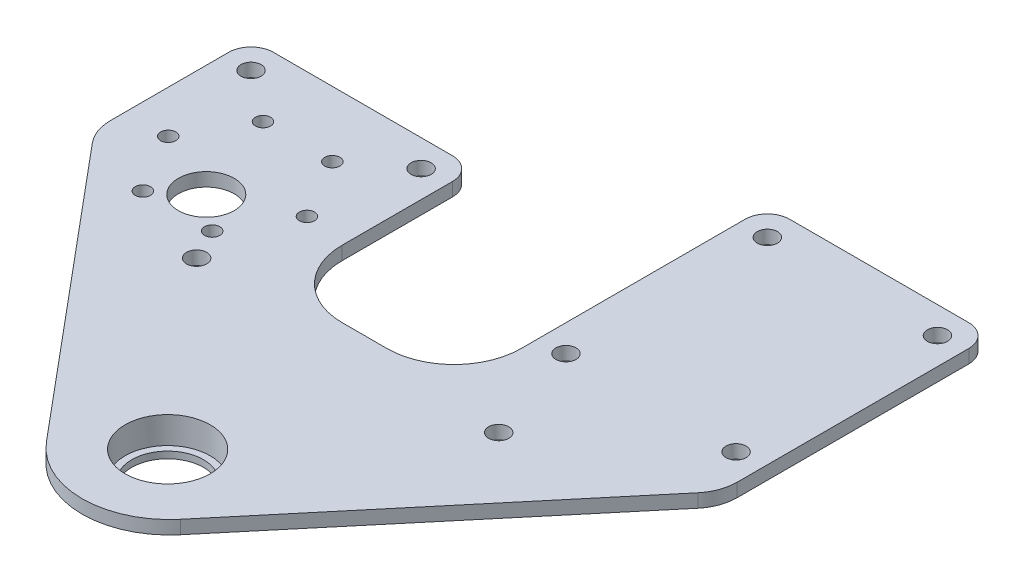
SolidWorks part; units mm, degrees
material "ABS"
ref_plane "Front Plane" through (0, 0, 0) normal (0, 0, 1) x (1, 0, 0)
ref_plane "Top Plane" through (0, 0, 0) normal (0, 1, 0) x (1, 0, 0)
ref_plane "Right Plane" through (0, 0, 0) normal (1, 0, 0) x (0, 0, -1)
sketch "Sketch2" plane through (0, 0, 0) normal (0, 1, 0) x (1, 0, 0)
  line L0 (-69.9951, 83.6231) -> (-69.9951, 57.2559)
  line L1 (-67.6634, 50.8374) -> (-14.9531, -12.1356)
  line L2 (14.9531, -12.1356) -> (67.6634, 50.8374)
  line L3 (69.9951, 57.2559) -> (69.9951, 109)
  line L4 (64.9951, 114) -> (24.9951, 114)
  line L5 (19.9951, 109) -> (19.9951, 59)
  line L6 (4.9951, 44) -> (-4.9951, 44)
  line L7 (-19.9951, 59) -> (-19.9951, 83.6231)
  line L8 (-24.9951, 88.6231) -> (-64.9951, 88.6231)
  line L9 (0, 0) -> (-123.0223, 0) construction
  line L10 (0, -30) -> (0, 0) construction
  line L11 (0, 0) -> (-44.9951, 53.6231) construction
  line L12 (0, 0) -> (44.9951, 53.6231) construction
  line L13 (-44.9951, 53.6231) -> (-69.9951, 53.6231) construction
  line L14 (-44.9951, 53.6231) -> (-19.9951, 53.6231) construction
  line L15 (0, 0) -> (0, 44) construction
  line L16 (44.9951, 53.6231) -> (69.9951, 53.6231) construction
  line L17 (44.9951, 53.6231) -> (19.9951, 53.6231) construction
  line L18 (-44.9951, 53.6231) -> (-44.9951, 60.6231) construction
  line L19 (19.9951, 108) -> (69.9951, 108) construction
  line L20 (-69.9951, 82.6231) -> (-19.9951, 82.6231) construction
  line L21 (-44.9951, 60.6231) -> (-60.4951, 60.6231) construction
  line L22 (19.9951, 63) -> (69.9951, 63) construction
  circle A0 centre (0, 0) radius 9.5
  circle A1 centre (0, 0) radius 70 construction
  circle A2 centre (-44.9951, 53.6231) radius 6.25
  arc A3 (14.9531, -12.1356) -> (-14.9531, -12.1356) centre (0, 0.3806) cw
  arc A4 (-4.9951, 44) -> (-19.9951, 59) centre (-4.9951, 59) cw
  arc A5 (19.9951, 59) -> (4.9951, 44) centre (4.9951, 59) cw
  circle A6 centre (-44.9951, 60.6231) radius 15.5 construction
  circle A7 centre (-60.4951, 60.6231) radius 1.7
  circle A8 centre (-52.7451, 74.0465) radius 1.7
  circle A9 centre (-37.2451, 74.0465) radius 1.7
  circle A10 centre (-29.4951, 60.6231) radius 1.7
  circle A11 centre (-37.2451, 47.1997) radius 1.7
  circle A12 centre (-52.7451, 47.1997) radius 1.7
  circle A13 centre (0, 0) radius 40.8 construction
  circle A14 centre (0, 0) radius 52.5 construction
  circle A15 centre (-33.7463, 40.2173) radius 2.25
  circle A16 centre (33.7463, 40.2173) radius 2.25
  circle A17 centre (25.9951, 108) radius 2.25
  circle A18 centre (63.9951, 108) radius 2.25
  arc A19 (69.9951, 109) -> (64.9951, 114) centre (64.9951, 109) ccw
  arc A20 (24.9951, 114) -> (19.9951, 109) centre (24.9951, 109) ccw
  arc A21 (-19.9951, 83.6231) -> (-24.9951, 88.6231) centre (-24.9951, 83.6231) ccw
  arc A22 (-69.9951, 83.6231) -> (-64.9951, 88.6231) centre (-64.9951, 83.6231) cw
  circle A23 centre (-63.9951, 82.6231) radius 2.25
  circle A24 centre (-25.9951, 82.6231) radius 2.25
  circle A25 centre (25.9951, 63) radius 2.25
  circle A26 centre (63.9951, 63) radius 2.25
  arc A27 (67.6634, 50.8374) -> (69.9951, 57.2559) centre (59.9951, 57.2559) ccw
  arc A28 (-69.9951, 57.2559) -> (-67.6634, 50.8374) centre (-59.9951, 57.2559) ccw
  point P51 (-44.9951, 60.6231)
  point P61 (19.9951, 114)
  point P66 (-69.9951, 88.6231)
  dimension "D1" = 19
  dimension "D3" = 140
  dimension "D5" = 12.5
  dimension "D7" = 19.5
  dimension "D9" = 15
  dimension "D10" = 15
  dimension "D11" = 7
  dimension "D12" = 31
  dimension "D15" = 3.4
  dimension "D14" = 81.6
  dimension "D18" = 105
  dimension "D19" = 4.5
  dimension "D20" = 4.5
  dimension "D22" = 4.5
  dimension "D23" = 4.5
  dimension "D26" = 5
  dimension "D27" = 5
  dimension "D29" = 4.5
  dimension "D31" = 4.5
  dimension "D34" = 4.5
  dimension "D35" = 4.5
  dimension "D40" = 10
  dimension "D2" = 30
  dimension "D4" = 50
  dimension "D6" = 50
  dimension "D8" = 44
  dimension "D13" = 70
  dimension "D17" = 35
  dimension "D21" = 6
  dimension "D24" = 6
  dimension "D25" = 6
  dimension "D28" = 6
  dimension "D30" = 6
  dimension "D32" = 6
  dimension "D33" = 45
  dimension "D36" = 6
  dimension "D37" = 6
  dimension "D38" = 25
  dimension "D39" = 25
  dimension "D16" = 6
extrude "Boss-Extrude1" add sketch "Sketch2" along normal blind 3
sketch "Sketch3" plane through (0, 0, 0) normal (0, -1, 0) x (-1, 0, 0)
  circle A0 centre (0, 0) radius 12.5
  circle A1 centre (0, 0) radius 9.5
  dimension "D1" = 19
  dimension "D2" = 25
extrude "Boss-Extrude2" add sketch "Sketch3" along normal blind 3
sketch "Sketch4" plane through (0, -3, 0) normal (0, -1, 0) x (-1, 0, 0)
  circle A0 centre (0, 0) radius 12.5
  circle A1 centre (0, 0) radius 8
  dimension "D1" = 25
  dimension "D2" = 16
extrude "Boss-Extrude3" add sketch "Sketch4" along normal blind 1.5
fillet "Fillet1" radius 2 1 edges at (0, 0, -12.5)
